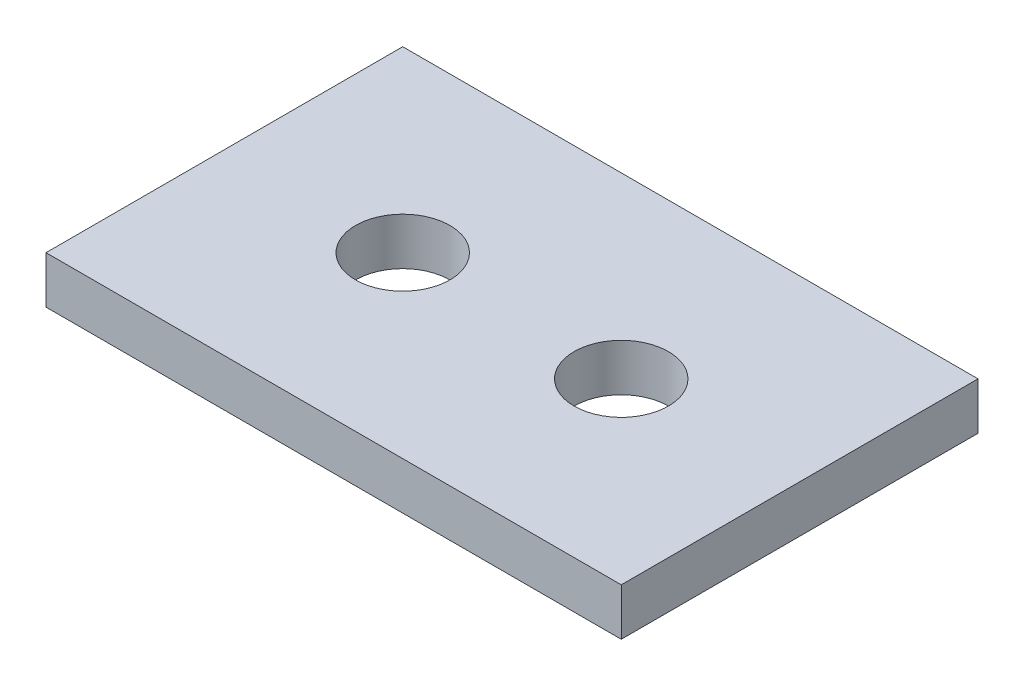
SolidWorks part; units mm, degrees
ref_plane "Front Plane" through (0, 0, 0) normal (0, 0, 1) x (1, 0, 0)
ref_plane "Top Plane" through (0, 0, 0) normal (0, 1, 0) x (1, 0, 0)
ref_plane "Right Plane" through (0, 0, 0) normal (1, 0, 0) x (0, 0, -1)
sketch "Sketch1" plane through (0, 0, 0) normal (0, 1, 0) x (1, 0, 0)
  line L0 (-3.675, 0) -> (3.675, 0) construction
  line L1 (9.675, -6) -> (-9.675, -6)
  line L2 (9.675, -6) -> (9.675, 6)
  line L3 (9.675, 6) -> (-9.675, 6)
  line L4 (-9.675, -6) -> (-9.675, 6)
  line L5 (9.675, -6) -> (-9.675, 6) construction
  line L6 (9.675, 6) -> (-9.675, -6) construction
  circle A0 centre (-3.675, 0) radius 1.5875
  circle A1 centre (3.675, 0) radius 1.5875
  circle A2 centre (-3.675, 0) radius 5 construction
  point P0 (0, 0)
  point P8 (0, 0)
  dimension "D1" = 3.175
  dimension "D4" = 10
  dimension "D2" = 7.35
  dimension "D3" = 12
  dimension "D5" = 6
extrude "Boss-Extrude1" add sketch "Sketch1" along normal mid plane 1.5875
